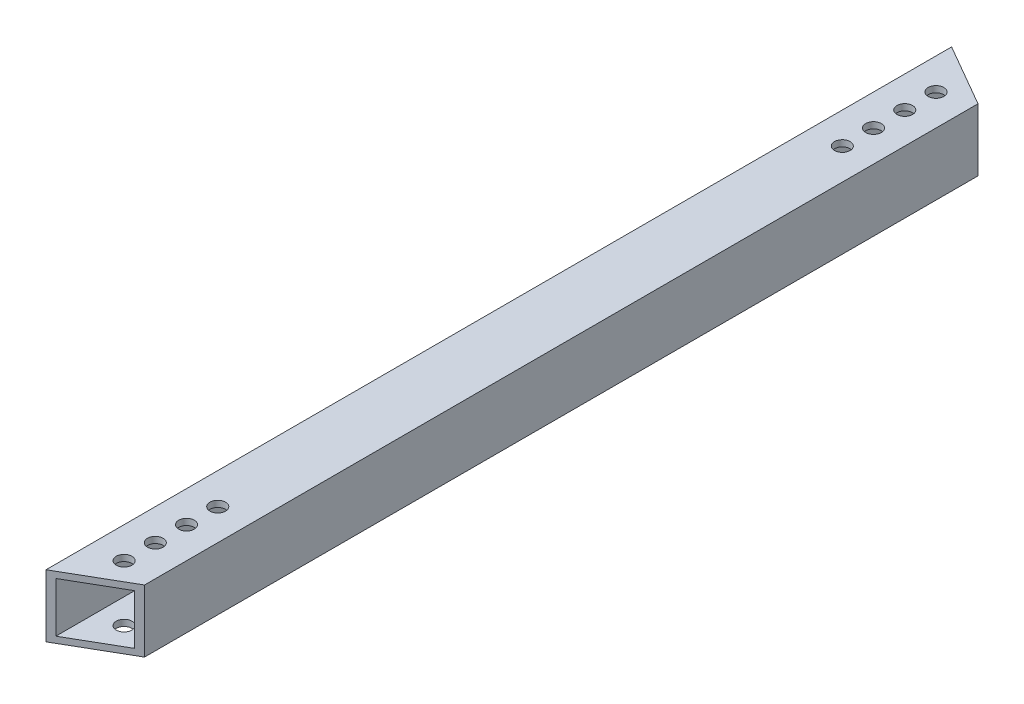
SolidWorks part; units mm, degrees
ref_plane "Front Plane" through (0, 0, 0) normal (0, 0, 1) x (1, 0, 0)
ref_plane "Top Plane" through (0, 0, 0) normal (0, 1, 0) x (1, 0, 0)
ref_plane "Right Plane" through (0, 0, 0) normal (1, 0, 0) x (0, 0, -1)
sketch "Sketch1" plane through (0, 0, 0) normal (0, 0, 1) x (1, 0, 0)
  line L0 (-10.16, 10.16) -> (10.16, 10.16)
  line L1 (-12.7, -12.7) -> (12.7, -12.7)
  line L2 (-12.7, -12.7) -> (-12.7, 12.7)
  line L3 (-12.7, 12.7) -> (12.7, 12.7)
  line L4 (12.7, -12.7) -> (12.7, 12.7)
  line L5 (-12.7, -12.7) -> (12.7, 12.7) construction
  line L6 (-12.7, 12.7) -> (12.7, -12.7) construction
  line L7 (10.16, -10.16) -> (10.16, 10.16)
  line L8 (-10.16, -10.16) -> (10.16, -10.16)
  line L9 (-10.16, -10.16) -> (-10.16, 10.16)
  point P0 (0, 0)
  dimension "D1" = 25.4
  dimension "D2" = 25.4
  dimension "D3" = 2.54
extrude "Boss-Extrude2" add sketch "Sketch1" along normal blind 368.3
sketch "Sketch2" plane through (0, 12.7, 0) normal (0, 1, 0) x (1, 0, 0)
  line L0 (-12.7, -368.3) -> (12.7, -353.6353)
  line L1 (12.7, -368.3) -> (12.7, 0) construction
  line L2 (12.7, -353.6353) -> (12.7, -368.3)
  line L3 (12.7, -368.3) -> (-12.7, -368.3)
  line L4 (-12.7, -184.15) -> (12.7, -184.15) construction
  line L5 (-12.7, -368.3) -> (-12.7, 0) construction
  line L6 (12.7, 0) -> (-12.7, 0)
  line L7 (12.7, -14.6647) -> (12.7, 0)
  line L8 (-12.7, 0) -> (12.7, -14.6647)
  dimension "D1" = 30
extrude "Cut-Extrude1" cut sketch "Sketch2" against normal through all
sketch "Sketch3" plane through (0, 12.7, 0) normal (0, 1, 0) x (1, 0, 0)
  line L0 (0, -7.3323) -> (0, -360.9677) construction
  line L1 (-12.7, 0) -> (12.7, -14.6647) construction
  line L2 (12.7, -353.6353) -> (-12.7, -368.3) construction
  circle A5 centre (0, -349.25) radius 3.175
  circle A6 centre (0, -336.55) radius 3.175
  circle A7 centre (0, -323.85) radius 3.175
  circle A8 centre (0, -311.15) radius 3.175
  circle A11 centre (0, -57.15) radius 3.175
  circle A12 centre (0, -44.45) radius 3.175
  circle A13 centre (0, -31.75) radius 3.175
  circle A14 centre (0, -19.05) radius 3.175
  arc A16 (0, -295.275) -> (0, -301.625) centre (0, -298.45) ccw [skipped]
  dimension "D3" = 6.35
  dimension "D5" = 5
extrude "Cut-Extrude2" cut sketch "Sketch3" against normal through all
